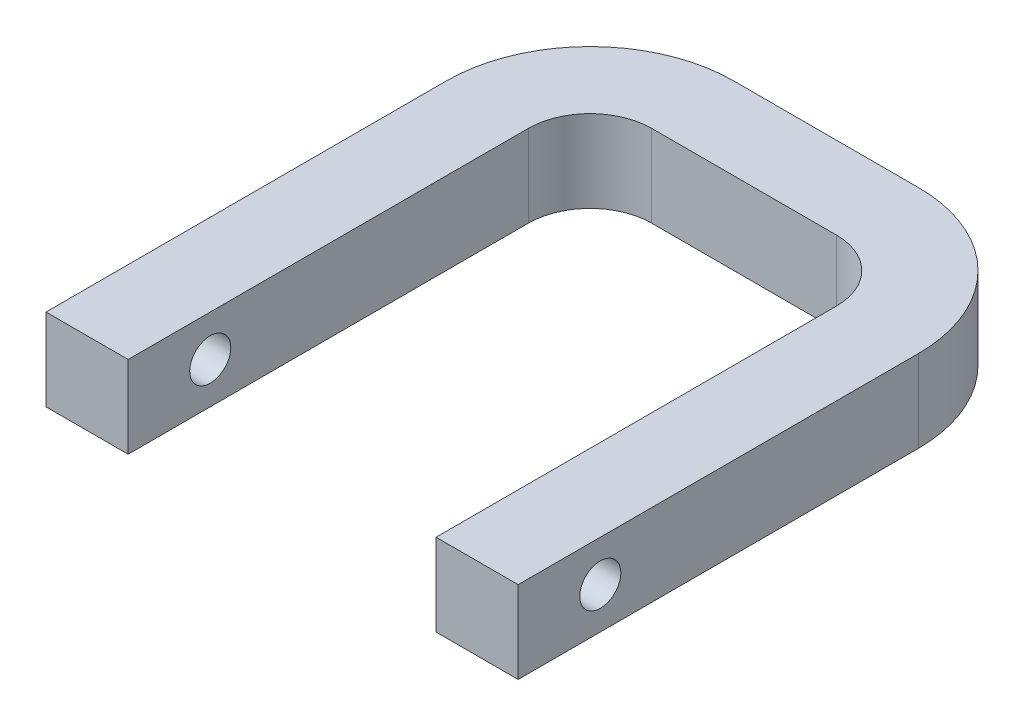
SolidWorks part; units mm, degrees
ref_plane "Front Plane" through (0, 0, 0) normal (0, 0, 1) x (1, 0, 0)
ref_plane "Top Plane" through (0, 0, 0) normal (0, 1, 0) x (1, 0, 0)
ref_plane "Right Plane" through (0, 0, 0) normal (1, 0, 0) x (0, 0, -1)
ref_axis "Z" through (0, 0, -2.65) along (0, 0, 1)
sketch "Sketch1" plane through (0, 0, 0) normal (0, 1, 0) x (1, 0, 0)
  line L0 (-9, 0) -> (9, 0)
  line L1 (-23, -14) -> (-23, -53)
  line L2 (-23, -53) -> (-15, -53)
  line L3 (-15, -53) -> (-15, -14)
  line L4 (-9, -8) -> (9, -8)
  line L5 (0, -8) -> (0, 0) construction
  line L6 (15, -53) -> (15, -14)
  line L7 (23, -53) -> (15, -53)
  line L8 (23, -14) -> (23, -53)
  arc A0 (-9, 0) -> (-23, -14) centre (-9, -14) ccw
  arc A1 (-15, -14) -> (-9, -8) centre (-9, -14) cw
  arc A2 (15, -14) -> (9, -8) centre (9, -14) ccw
  arc A3 (9, 0) -> (23, -14) centre (9, -14) cw
  dimension "D3" = 6
  dimension "D1" = 30
  dimension "D2" = 8
  dimension "D4" = 45
extrude "Boss-Extrude1" add sketch "Sketch1" along normal blind 4 and the other way blind 4
sketch "Sketch2" plane through (15, 0, 0) normal (-1, 0, 0) x (0, 0, 1)
  line L1 (23.1, 0) -> (-23.1, 0) construction
  line L2 (0, -4.4) -> (0, 4.4) construction
  circle A0 centre (45, 0) radius 2
  dimension "D1" = 4
  dimension "D2" = 45
extrude "Cut-Extrude1" cut sketch "Sketch2" against normal through all both and the other way through all
ref_axis "Axis2" through (-26.6767, 0, 45) along (1, 0, 0)
equation "\"width\"= \"EyeDiameter\" + \"EyeClearance\""
equation "\"prongwidth\"= 8"
equation "\"D2@Sketch1\"=\"prongwidth\""
equation "\"D1@Sketch1\"=\"width\""
equation "\"D3@Sketch1\"=\"width\"/5"
equation "\"pronglength\"= \"BasePlaneDistance\"'model implicitly adds clearance (of prongwidth) to the hole drilled at the baseplanedistance"
equation "\"D4@Sketch1\"=\"pronglength\""
equation "\"D1@Boss-Extrude1\"=\"prongwidth\"/2"
equation "\"D2@Boss-Extrude1\"=\"prongwidth\"/2"
equation "\"lbracket-plane-to-axis\"= \"BasePlaneDistance\""
equation "\"D2@Sketch2\"=\"lbracket-plane-to-axis\""
equation "\"EyeDiameter\" = 28"
equation "\"BasePlaneDistance\" = 45"
equation "\"EyeClearance\" = 2"
